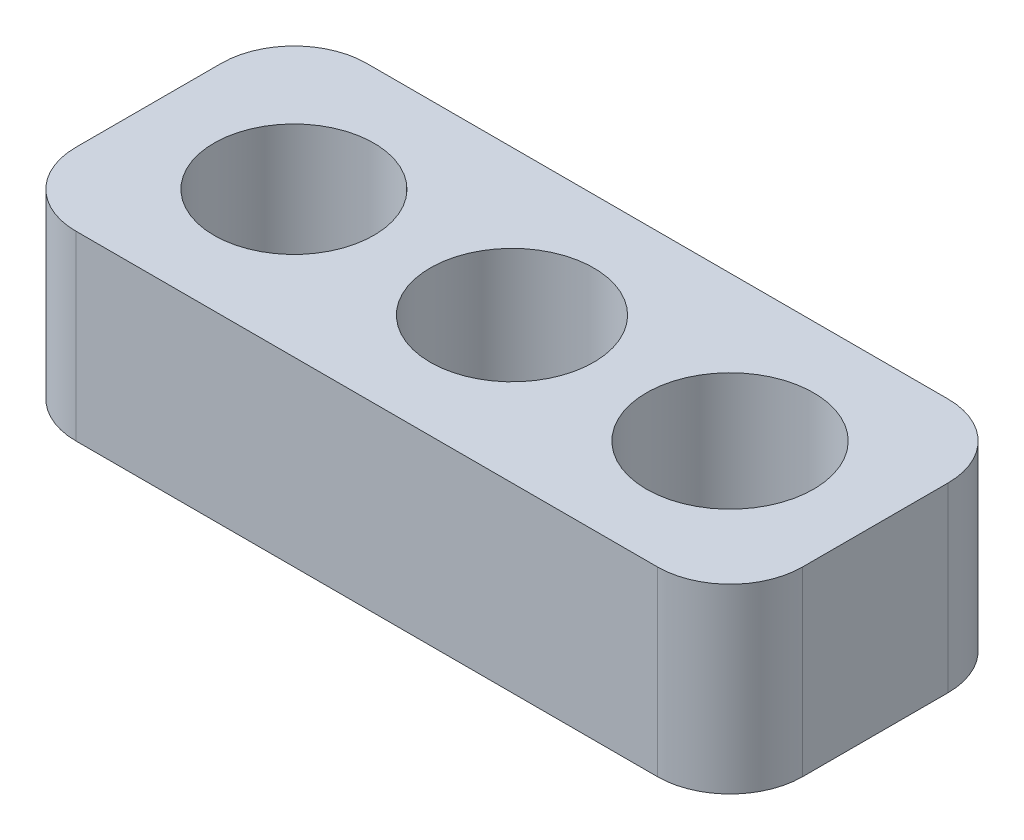
SolidWorks part; units mm, degrees
ref_plane "Front Plane" through (0, 0, 0) normal (0, 0, 1) x (1, 0, 0)
ref_plane "Top Plane" through (0, 0, 0) normal (0, 1, 0) x (1, 0, 0)
ref_plane "Right Plane" through (0, 0, 0) normal (1, 0, 0) x (0, 0, -1)
ref_axis "X" through (-88.99, 0, 0) along (1, 0, 0)
ref_axis "Y" through (0, 55, 0) along (0, -1, 0)
ref_axis "Z" through (0, 0, -88.99) along (0, 0, 1)
sketch "Sketch1" plane through (0, 0, 0) normal (0, 1, 0) x (1, 0, 0)
  line L0 (-6, 0) -> (6, 0) construction
  line L1 (-10, 4) -> (10, 4)
  line L2 (-10, 4) -> (-10, -4)
  line L3 (-10, -4) -> (10, -4)
  line L4 (10, 4) -> (10, -4)
  line L5 (-10, 4) -> (10, -4) construction
  line L6 (-10, -4) -> (10, 4) construction
  circle A0 centre (-6, 0) radius 2.2
  circle A1 centre (0, 0) radius 2.25
  circle A2 centre (6, 0) radius 2.3
  point P0 (0, 0)
  point P9 (0, 0)
  dimension "D1" = 4.5
  dimension "D2" = 4.6
  dimension "D3" = 4.4
  dimension "D4" = 12
  dimension "D5" = 8
  dimension "D6" = 20
extrude "Boss-Extrude1" add sketch "Sketch1" along normal blind 5
fillet "Fillet1" radius 2 4 edges at (-10, 2.5, -4) (-10, 2.5, 4) (10, 2.5, -4) (10, 2.5, 4)
